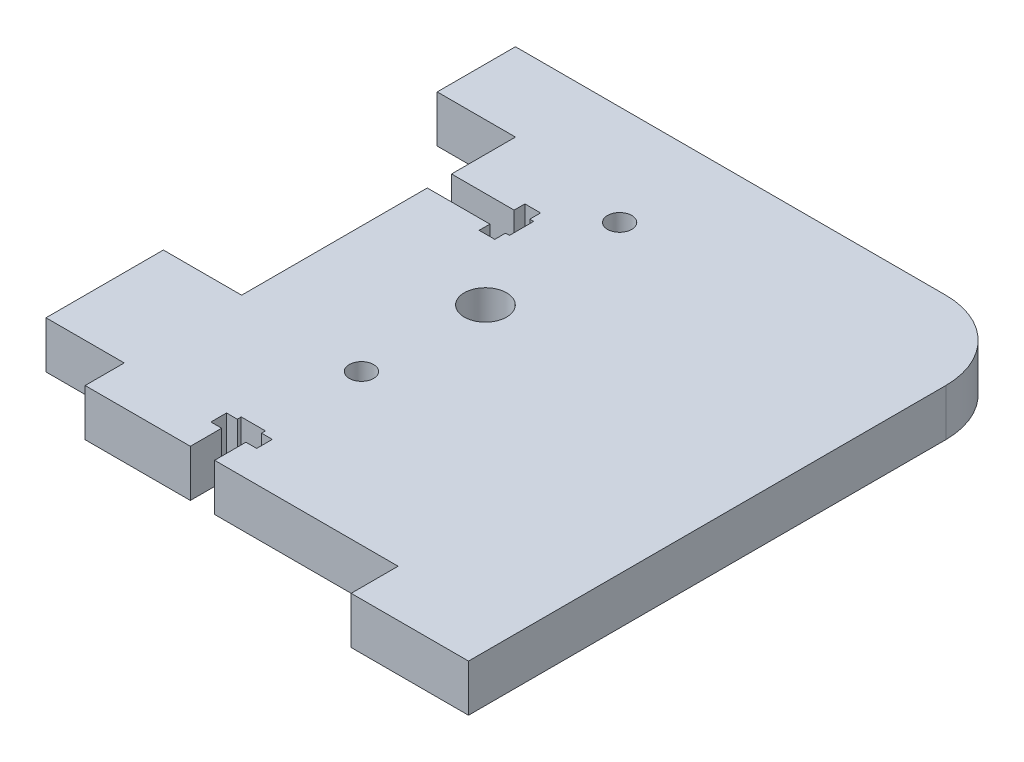
SolidWorks part; units mm, degrees
ref_plane "Płaszczyzna przednia" through (0, 0, 0) normal (0, 0, 1) x (1, 0, 0)
ref_plane "Płaszczyzna górna" through (0, 0, 0) normal (0, 1, 0) x (1, 0, 0)
ref_plane "Płaszczyzna prawa" through (0, 0, 0) normal (1, 0, 0) x (0, 0, -1)
sketch "Szkic1" plane through (0, -418.8763, -418.8763) normal (0, 1, 0) x (1, 0, 0)
  line L1 (-1165.3685, -408.8763) -> (-1142.3685, -408.8763)
  line L2 (-1165.3685, -479.8763) -> (-1165.3685, -408.8763)
  line L3 (-1142.3685, -408.8763) -> (-1142.3685, -459.8763)
  line L4 (-1165.3685, -479.8763) -> (-1100.3685, -479.8763)
  line L5 (-1100.3685, -459.8763) -> (-1100.3685, -479.8763)
  line L7 (-1100.3685, -459.8763) -> (-1142.3685, -459.8763)
  line L10 (-482.1641, -408.8763) -> (-356.3685, -408.8763) construction
  dimension "D1" = 0
  dimension "D2" = 65
  dimension "D3" = 23
  dimension "D5" = 20
extrude "Dodanie-wyciągnięcie2" add sketch "Szkic1" along normal blind 3 and the other way blind 3
sketch "Szkic2" plane through (0, 0, 61) normal (0, 0, 1) x (1, 0, 0)
  line L0 (-1165.3685, -415.8763) -> (-1100.3685, -415.8763) construction
  line L1 (-1165.3685, -421.8763) -> (-1115.3685, -421.8763)
  line L2 (-1165.3685, -421.8763) -> (-1165.3685, -415.8763)
  line L3 (-1165.3685, -415.8763) -> (-1115.3685, -415.8763)
  line L4 (-1115.3685, -421.8763) -> (-1115.3685, -415.8763)
  dimension "D1" = 50
extrude "Wytnij-wyciągnięcie1" cut sketch "Szkic2" against normal blind 6
sketch "Szkic3" plane through (0, -415.8763, 0) normal (0, 1, 0) x (1, 0, 0)
  line L0 (-1115.3685, -55) -> (-1165.3685, -55) construction
  line L1 (-1138.8185, -55) -> (-1141.9185, -55)
  line L2 (-1138.8185, -55) -> (-1138.8185, -51)
  line L3 (-1138.8185, -48.5) -> (-1141.9185, -48.5)
  line L4 (-1141.9185, -55) -> (-1141.9185, -51)
  line L5 (-1138.8185, -49) -> (-1138.8185, -48.5)
  line L6 (-1137.4435, -49) -> (-1138.8185, -49)
  line L7 (-1137.4435, -49) -> (-1137.4435, -51)
  line L8 (-1137.4435, -51) -> (-1138.8185, -51)
  line L9 (-1143.2935, -49) -> (-1143.2935, -51)
  line L10 (-1141.9185, -49) -> (-1143.2935, -49)
  line L11 (-1141.9185, -49) -> (-1141.9185, -48.5)
  line L12 (-1141.9185, -51) -> (-1143.2935, -51)
  line L13 (-1165.3685, 10) -> (-1165.3685, -55) construction
  point P14 (-1140.3685, -55)
  dimension "D1" = 6.5
  dimension "D2" = 3.1
  dimension "D3" = 5.85
  dimension "D4" = 1.375
  dimension "D5" = 0.5
  dimension "D6" = 2
  dimension "D7" = 25
extrude "Wytnij-wyciągnięcie2" cut sketch "Szkic3" against normal blind 6
sketch "Szkic4" plane through (0, -415.8763, 0) normal (0, 1, 0) x (1, 0, 0)
  line L0 (-1165.3685, 10) -> (-1165.3685, -55) construction
  line L1 (-1165.3685, 0) -> (-1155.3685, 0)
  line L2 (-1165.3685, 0) -> (-1165.3685, -35)
  line L3 (-1165.3685, -35) -> (-1155.3685, -35)
  line L4 (-1155.3685, 0) -> (-1155.3685, -35)
  line L5 (-1142.3685, 10) -> (-1165.3685, 10) construction
  line L6 (-1141.9185, -55) -> (-1165.3685, -55) construction
  line L8 (-1165.3685, -55) -> (-1155.3685, -55)
  line L9 (-1165.3685, -55) -> (-1165.3685, -50)
  line L10 (-1165.3685, -50) -> (-1155.3685, -50)
  line L11 (-1155.3685, -55) -> (-1155.3685, -50)
  dimension "D1" = 10
  dimension "D2" = 20
  dimension "D3" = 10
  dimension "D4" = 10
  dimension "D5" = 5
extrude "Wytnij-wyciągnięcie3" cut sketch "Szkic4" against normal blind 6
sketch "Szkic5" plane through (0, -415.8763, 0) normal (0, 1, 0) x (1, 0, 0)
  line L0 (-1155.3685, -35) -> (-1155.3685, 0) construction
  line L1 (-1155.3685, -8.1682) -> (-1147.3685, -8.1682)
  line L2 (-1155.3685, -8.1682) -> (-1155.3685, -11.2682)
  line L3 (-1155.3685, -11.2682) -> (-1147.3685, -11.2682)
  line L4 (-1144.8685, -8.1682) -> (-1144.8685, -11.2682)
  line L5 (-1145.3685, -8.1682) -> (-1145.3685, -6.7932)
  line L6 (-1145.3685, -12.6432) -> (-1147.3685, -12.6432)
  line L7 (-1145.3685, -12.6432) -> (-1145.3685, -11.2682)
  line L8 (-1145.3685, -6.7932) -> (-1147.3685, -6.7932)
  line L9 (-1147.3685, -12.6432) -> (-1147.3685, -11.2682)
  line L10 (-1145.3685, -11.2682) -> (-1144.8685, -11.2682)
  line L11 (-1147.3685, -8.1682) -> (-1147.3685, -6.7932)
  line L12 (-1145.3685, -8.1682) -> (-1144.8685, -8.1682)
  dimension "D1" = 3.1
  dimension "D2" = 0.5
  dimension "D3" = 5.85
  dimension "D4" = 1.375
  dimension "D5" = 2
  dimension "D6" = 10.5
extrude "Wytnij-wyciągnięcie4" cut sketch "Szkic5" against normal blind 6
ref_plane "Płaszczyzna1" through (-705.3685, 0, 0) normal (-1, 0, 0) x (0, 0, 1)
sketch "Szkic9" plane through (0, -415.8763, 0) normal (0, 1, 0) x (1, 0, 0)
  line L0 (-1142.3685, 10) -> (-1142.3685, -41)
  line L1 (-1142.3685, 10) -> (-1110.3685, 10)
  line L2 (-1142.3685, -41) -> (-1100.3685, -41)
  line L3 (-1100.3685, 0) -> (-1100.3685, -41)
  line L4 (-1100.3685, -61) -> (-1100.3685, -41) construction
  arc A0 (-1110.3685, 10) -> (-1100.3685, 0) centre (-1110.3685, 0) cw
  dimension "D1" = 10
  dimension "D2" = 0
extrude "Dodanie-wyciągnięcie3" add sketch "Szkic9" against normal blind 6 separate body
combine bodies "Połącz3" operation type add bodies to combine 111 108
sketch "Szkic8" plane through (0, -421.8763, 0) normal (0, -1, 0) x (1, 0, 0)
  circle A0 centre (-1139.2648, 35.7898) radius 1.55 construction
  circle A1 centre (-1139.2648, 2.7898) radius 1.55 construction
  circle A2 centre (-1139.2648, 35.7898) radius 1.55
  circle A3 centre (-1138.7056, 20.5) radius 2.5 construction
  circle A5 centre (-1139.2648, 2.7898) radius 1.55
  circle A6 centre (-1138.7056, 20.5) radius 2.7
  dimension "D1" = 0
extrude "Wytnij-wyciągnięcie5" cut sketch "Szkic8" against normal blind 6
equation "\"tolerancja_wpusy\"=0.2"
equation "\"dlugosc_wpustu_duzy\"=20"
equation "\"srednica_otworu_M3\"=3.1"
equation "\"szerokosc_nogi_T\"=3.1"
equation "\"dlugosc_T_30\"=11"
equation "\"grubosc_na_nakretke_kwadrat\"=2"
equation "\"szerokosc_na_nakretke_kwadrat\"=5.85"
equation "\"wyokosc_nadstawki_T\"=0.5"
equation "\"dlugosc_T_20_6\"=14"
equation "\"D2@Szkic3\"=\"szerokosc_nogi_T\""
equation "\"D3@Szkic3\"=\"szerokosc_na_nakretke_kwadrat\""
equation "\"D4@Szkic3\"=(\"szerokosc_na_nakretke_kwadrat\"-\"szerokosc_nogi_T\")/2"
equation "\"D5@Szkic3\"=\"wyokosc_nadstawki_T\""
equation "\"D6@Szkic3\"=\"grubosc_na_nakretke_kwadrat\""
equation "\"D1@Szkic5\"=\"szerokosc_nogi_T\""
equation "\"D2@Szkic5\"=\"wyokosc_nadstawki_T\""
equation "\"D3@Szkic5\"=\"szerokosc_na_nakretke_kwadrat\""
equation "\"D4@Szkic5\"=(\"szerokosc_na_nakretke_kwadrat\"-\"szerokosc_nogi_T\")/2"
equation "\"D5@Szkic5\"=\"grubosc_na_nakretke_kwadrat\""
